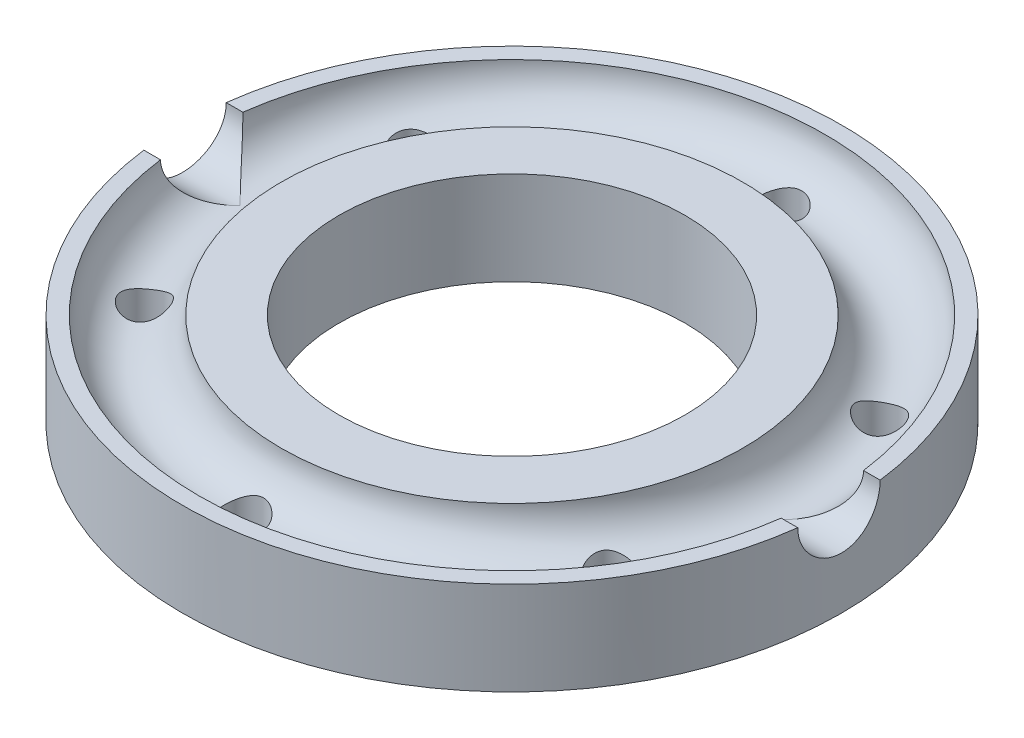
SolidWorks part; units mm, degrees
ref_plane "Front Plane" through (0, 0, 0) normal (0, 0, 1) x (1, 0, 0)
ref_plane "Top Plane" through (0, 0, 0) normal (0, 1, 0) x (1, 0, 0)
ref_plane "Right Plane" through (0, 0, 0) normal (1, 0, 0) x (0, 0, -1)
ref_axis "Centerline" through (0, 55, 0) along (0, -1, 0)
sketch "Sketch1" plane through (0, 0, 0) normal (0, 1, 0) x (1, 0, 0)
  circle A0 centre (0, 0) radius 10.414
  circle A1 centre (0, 0) radius 8.001
  dimension "D1" = 20.828
  dimension "D2" = 16.002
extrude "Boss-Extrude1" add sketch "Sketch1" along normal blind 4.318
sketch "Sketch2" plane through (0, 0, 0) normal (0, -1, 0) x (1, 0, 0)
  circle A0 centre (0, 0) radius 8.001
  circle A1 centre (0, 0) radius 15.24
  dimension "D1" = 30.48
  dimension "D2" = 16.002
extrude "Boss-Extrude2" add sketch "Sketch2" along normal blind 4.318
sketch "Sketch3" plane through (0, 0, 0) normal (0, 0, 1) x (1, 0, 0)
  line L0 (15.24, 0) -> (-15.24, 0) construction
  line L1 (10.668, 9.5598) -> (10.668, -10.185) construction
  circle A0 centre (12.573, 0) radius 1.905
  dimension "D2" = 3.81
  dimension "D1" = 10.668
revolve "Cut-Revolve1" cut sketch "Sketch3" angle 360 about axis through (0, 55, 0) along (0, -1, 0)
sketch "Sketch4" plane through (0, 0, 0) normal (0, 1, 0) x (1, 0, 0)
  circle A0 centre (0, 12.446) radius 0.9525
  dimension "D1" = 1.905
  dimension "D2" = 12.446
extrude "Cut-Extrude1" cut sketch "Sketch4" against normal up to next
pattern_circular "CirPattern1" count 6 over 360 about axis through (0, 55, 0) along (0, -1, 0) of "Cut-Extrude1"
sketch "Sketch5" plane through (0, 4.318, 0) normal (0, 1, 0) x (1, 0, 0)
  circle A0 centre (0, 0) radius 10.414
  dimension "D1" = 20.828
extrude "Cut-Extrude2" cut sketch "Sketch5" against normal blind 4.318
ref_plane "Inlet Plane" through (15.24, 0, 0) normal (1, 0, 0) x (0, 0, -1)
sketch "Sketch8" plane through (15.24, 0, 0) normal (1, 0, 0) x (0, 0, -1)
  circle A0 centre (0, 0) radius 1.905
  dimension "D1" = 3.81
extrude "Cut-Extrude3" cut sketch "Sketch8" against normal up to next
pattern_circular "CirPattern2" count 2 over 360 about axis through (0, 55, 0) along (0, -1, 0) of "Cut-Extrude3"
